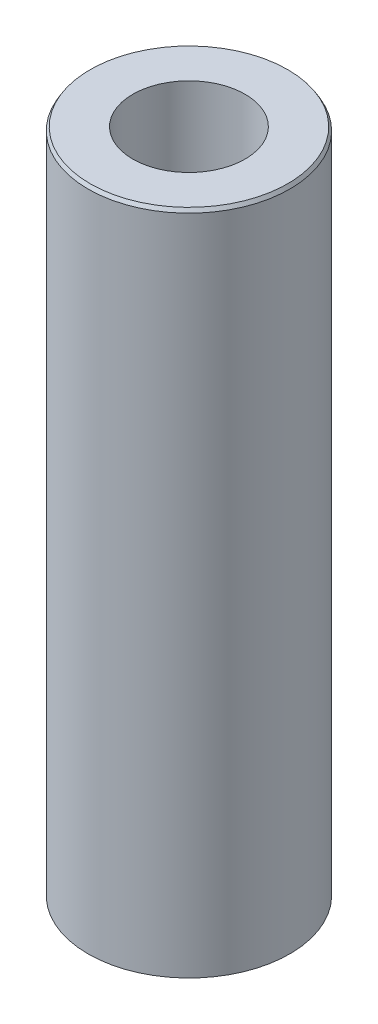
SolidWorks part; units mm, degrees
ref_plane "Front Plane" through (0, 0, 0) normal (0, 0, 1) x (1, 0, 0)
ref_plane "Top Plane" through (0, 0, 0) normal (0, 1, 0) x (1, 0, 0)
ref_plane "Right Plane" through (0, 0, 0) normal (1, 0, 0) x (0, 0, -1)
sketch "Sketch1" plane through (0, 0, 0) normal (0, 1, 0) x (1, 0, 0)
  circle A0 centre (0, 0) radius 42.5
  dimension "SHAFT_OD" = 85
extrude "Boss-Extrude1" add sketch "Sketch1" along normal blind 281.3747
sketch "Sketch2" plane through (0, 0, 0) normal (0, 1, 0) x (1, 0, 0)
  circle A0 centre (0, 0) radius 23.6645
  dimension "BORE_D" = 47.329
extrude "Cut-Extrude1" cut sketch "Sketch2" along normal through all
chamfer "Chamfer1" distance 1.5124 angle 30 2 edges at (0, 281.3747, 42.5) (0, 0, 42.5) first distance on face at (0, 281.3747, 42.5) first distance on face at (0, 0, 23.6645)
